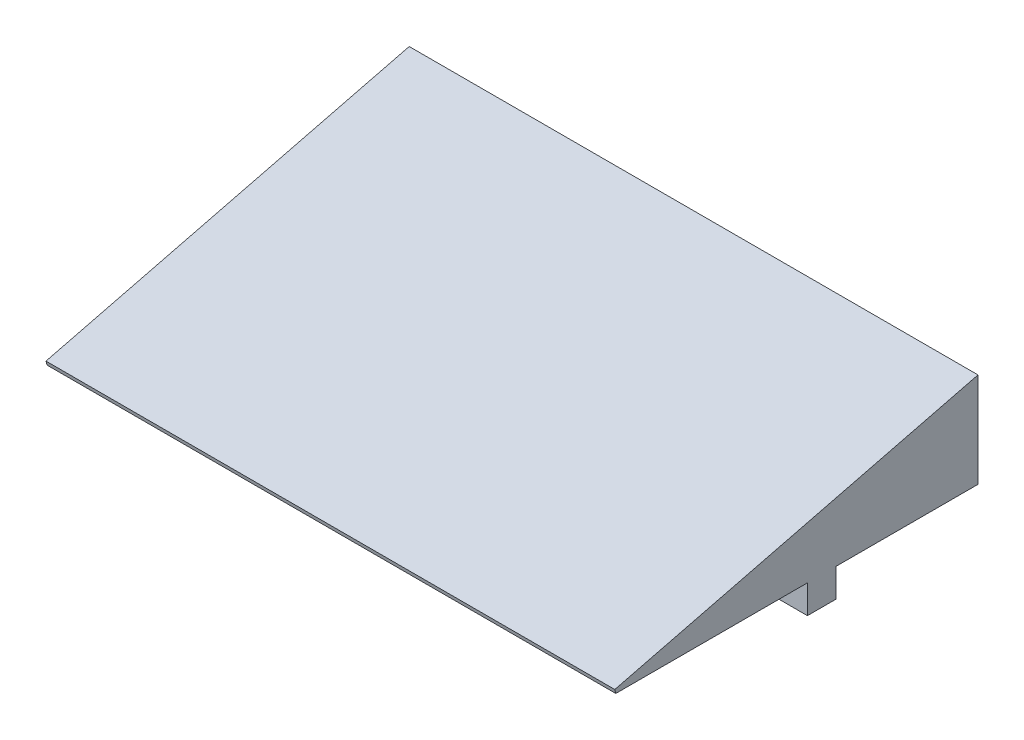
SolidWorks part; units mm, degrees
ref_plane "Front Plane" through (0, 0, 0) normal (0, 0, 1) x (1, 0, 0)
ref_plane "Top Plane" through (0, 0, 0) normal (0, 1, 0) x (1, 0, 0)
ref_plane "Right Plane" through (0, 0, 0) normal (1, 0, 0) x (0, 0, -1)
sketch "Sketch3" plane through (0, 0, 0) normal (0, 1, 0) x (1, 0, 0)
  line L1 (-60, 40) -> (60, 40)
  line L2 (-60, 40) -> (-60, -40)
  line L3 (-60, -40) -> (60, -40)
  line L4 (60, 40) -> (60, -40)
  line L5 (-60, 40) -> (60, -40) construction
  line L6 (-60, -40) -> (60, 40) construction
  point P0 (0, 0)
  dimension "D1" = 120
  dimension "D2" = 80
extrude "Boss-Extrude1" add sketch "Sketch3" along normal blind 20
sketch "Sketch4" plane through (60, 0, 0) normal (1, 0, 0) x (0, 0, -1)
  line L2 (-40, 0) -> (40, 0)
  line L3 (-39.9714, 0) -> (40, 20)
  line L4 (-38.6975, 0) -> (40, 0)
  line L5 (40, 20) -> (40, 0)
  line M4 (-40, 0) -> (40, 0)
  line M6 (40, 20) -> (-40, 20)
  line M7 (-40, 20) -> (-40, 0)
  dimension "D1" = 82.4343
extrude "Cut-Extrude3" cut sketch "Sketch4" against normal blind 120 and the other way through all contours L3 M4 M6 M7 region at (60, 13.3309, 13.3333)
sketch "Sketch5" plane through (60, 0, 0) normal (1, 0, 0) x (0, 0, -1)
  line L0 (4.0143, 0) -> (4.0143, -6)
  line L1 (-39.9714, 0) -> (40, 0) construction
  line L2 (4.0143, -6) -> (10.0143, -6)
  line L3 (10.0143, -6) -> (10.0143, 0)
  line L4 (-39.9714, 0) -> (4.0143, 0)
  line L5 (4.0143, 0) -> (10.0143, 0)
  line L7 (40, 20) -> (-39.9714, 0)
  line L8 (-39.9714, 0) -> (40, 0)
  line L9 (40, 0) -> (40, 20)
  line L10 (40, 20) -> (-39.9714, 0)
  line L11 (10.0143, 0) -> (40, 0)
  line L12 (40, 0) -> (40, 20)
  point P4 (0.0143, 0)
  line M4 (-39.9714, 0) -> (40, 0)
  dimension "D1" = 6
  dimension "D2" = 6
  dimension "D3" = 10
  dimension "D4" = 0
extrude "Boss-Extrude2" add sketch "Sketch5" against normal blind 120 contours L2 L3 L0 M4 region at (60, -3, -7.0143)
sketch "Sketch6" plane through (0, 9.408, 2.3528) normal (0, 0.9701, 0.2426) x (1, 0, 0)
  line L0 (-60, -38.7771) -> (-60, -35.3287)
  line L1 (-60, -38.7771) -> (-60, 43.6572) construction
  line L2 (-60, -35.3287) -> (60, -35.3287)
  line L3 (60, -38.7771) -> (60, 43.6572) construction
  line L4 (60, -35.3287) -> (60, -38.7771)
  line L5 (-60, -38.7771) -> (60, -38.7771) construction
  line L6 (60, -38.7771) -> (-60, -38.7771)
extrude "Cut-Extrude4" cut sketch "Sketch6" against normal blind 10
